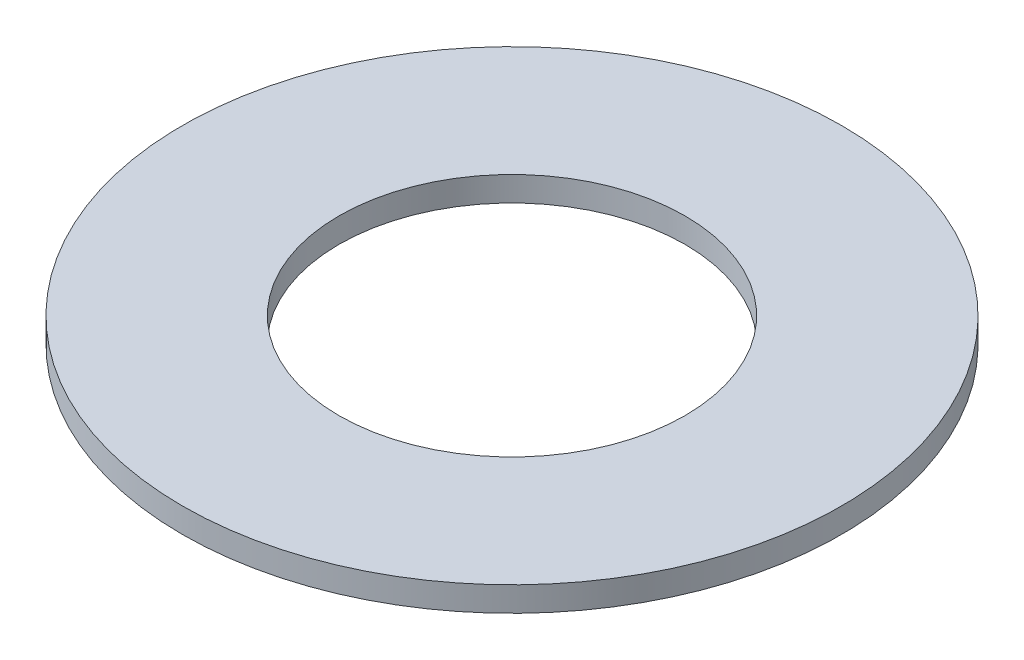
SolidWorks part; units mm, degrees
ref_plane "Front Plane" through (0, 0, 0) normal (0, 0, 1) x (1, 0, 0)
ref_plane "Top Plane" through (0, 0, 0) normal (0, 1, 0) x (1, 0, 0)
ref_plane "Right Plane" through (0, 0, 0) normal (1, 0, 0) x (0, 0, -1)
sketch "Sketch1" plane through (0, 0, 0) normal (0, 1, 0) x (1, 0, 0)
  circle A0 centre (0, 0) radius 10.16
  circle A1 centre (0, 0) radius 5.334
  dimension "D1" = 10.668
  dimension "D2" = 20.32
extrude "Boss-Extrude1" add sketch "Sketch1" along normal blind 0.762
